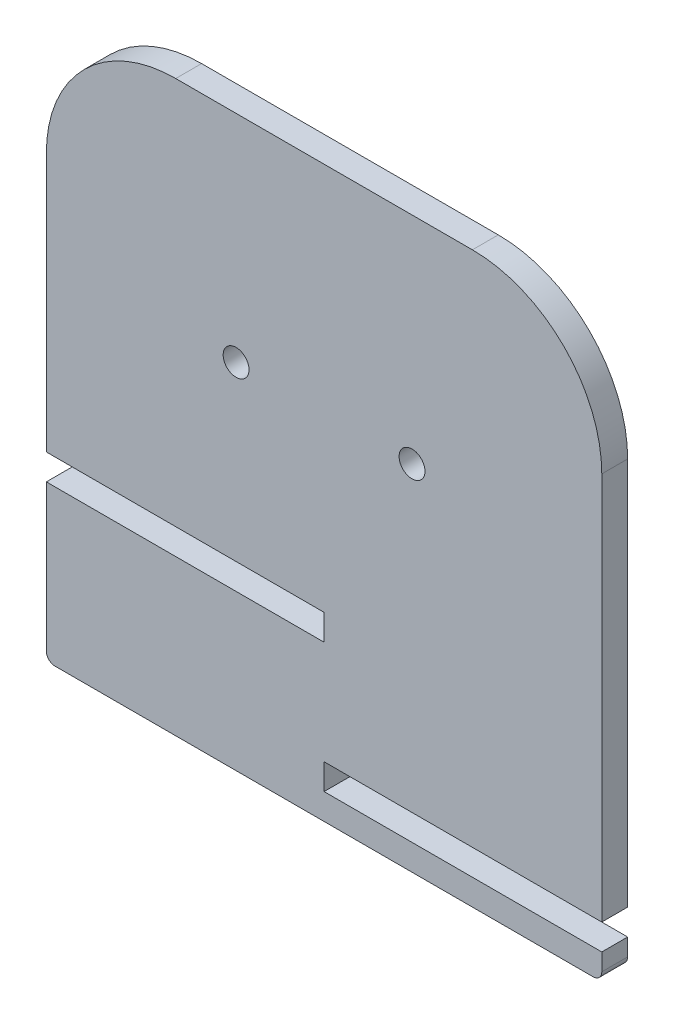
SolidWorks part; units mm, degrees
ref_plane "Front Plane" through (0, 0, 0) normal (0, 0, 1) x (1, 0, 0)
ref_plane "Top Plane" through (0, 0, 0) normal (0, 1, 0) x (1, 0, 0)
ref_plane "Right Plane" through (0, 0, 0) normal (1, 0, 0) x (0, 0, -1)
sketch "Sketch1" plane through (0, 0, 0) normal (0, 0, 1) x (1, 0, 0)
  line L0 (-46.6615, -6.4851) -> (-12.2615, -6.4851)
  line L12 (-61.6615, -21.4851) -> (-61.6615, -51.4851)
  line L13 (-61.6615, -51.4851) -> (-29.4615, -51.4851)
  line L15 (-61.6615, -54.4851) -> (-29.4615, -54.4851)
  line L16 (-29.4615, -51.4851) -> (-29.4615, -54.4851)
  line L17 (2.7385, -66.4851) -> (-29.4615, -66.4851)
  line L19 (2.7385, -69.4851) -> (-29.4615, -69.4851)
  line L20 (-29.4615, -66.4851) -> (-29.4615, -69.4851)
  line L21 (-61.6615, -54.4851) -> (-61.6615, -71.4851)
  line L22 (2.7385, -21.4851) -> (2.7385, -66.4851)
  line L23 (2.7385, -69.4851) -> (2.7385, -71.4851)
  line L24 (-60.6615, -72.4851) -> (1.7385, -72.4851)
  arc A0 (-12.2615, -6.4851) -> (2.7385, -21.4851) centre (-12.2615, -21.4851) cw
  arc A2 (-46.6615, -6.4851) -> (-61.6615, -21.4851) centre (-46.6615, -21.4851) ccw
  arc A3 (-61.6615, -71.4851) -> (-60.6615, -72.4851) centre (-60.6615, -71.4851) ccw
  arc A4 (1.7385, -72.4851) -> (2.7385, -71.4851) centre (1.7385, -71.4851) ccw
  point P6 (0, 0)
  dimension "D9" = 64.4
  dimension "D4" = 66
  dimension "D2" = 15
  dimension "D3" = 1
  dimension "D5" = 15
  dimension "D6" = 2
  dimension "D7" = 32.2
  dimension "D8" = 3
  dimension "D10" = 32.2
  dimension "D11" = 3
extrude "Boss-Extrude7" add sketch "Sketch1" along normal blind 3 contours L23 A4 L24 A3 L21 L15 L16 L13 L12 A2 L0 A0 L22 L17 L20 L19
sketch "Sketch3" plane through (0, 0, 3) normal (0, 0, 1) x (1, 0, 0)
  line L0 (-46.6615, -6.4851) -> (-12.2615, -6.4851) construction
  line L1 (2.7385, -21.4851) -> (2.7385, -66.4851) construction
  line L2 (-61.6615, -21.4851) -> (-61.6615, -51.4851) construction
  circle A0 centre (-19.2615, -31.4851) radius 1.5
  circle A1 centre (-39.6615, -31.4851) radius 1.5
  point P8 (0, 0)
  dimension "D1" = 25
  dimension "D3" = 22
  dimension "D2" = 22
  dimension "D4" = 25
extrude "Cut-Extrude1" cut sketch "Sketch3" against normal blind 3
